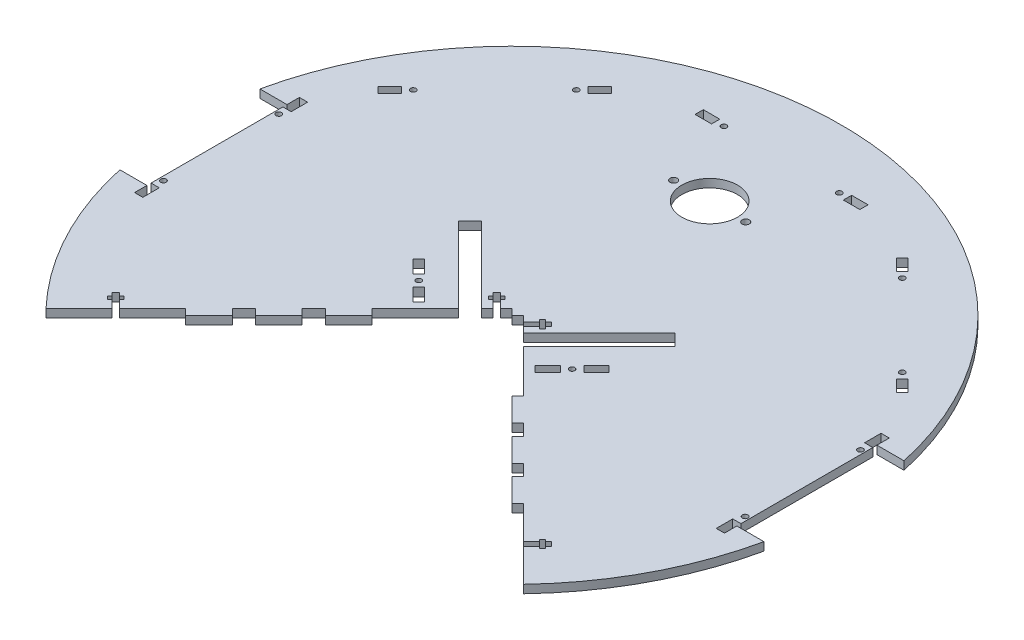
SolidWorks part; units mm, degrees
ref_plane "Front Plane" through (0, 0, 0) normal (0, 0, 1) x (1, 0, 0)
ref_plane "Top Plane" through (0, 0, 0) normal (0, 1, 0) x (1, 0, 0)
ref_plane "Right Plane" through (0, 0, 0) normal (1, 0, 0) x (0, 0, -1)
sketch "Sketch1" plane through (0, 0, 0) normal (0, 1, 0) x (1, 0, 0)
  circle A0 centre (0, 0) radius 254
  dimension "D1" = 508
extrude "Base Plate" add sketch "Sketch1" along normal blind 6.35
sketch "Sketch2" plane through (0, 6.35, 0) normal (0, 1, 0) x (1, 0, 0)
  line L0 (0, 0) -> (-179.6051, -179.6051)
  line L1 (0, -36.2008) -> (0, -54.9716) construction
  line L2 (0, 0) -> (179.6051, -179.6051)
  circle A0 centre (0, 0) radius 254 construction
  arc A1 (-179.6051, -179.6051) -> (179.6051, -179.6051) centre (0, 0) ccw
  dimension "D1" = 254
  dimension "D2" = 45
extrude "V Funnel Cut" cut sketch "Sketch2" against normal through all
sketch "Sketch4" plane through (0, 6.35, 0) normal (0, 1, 0) x (1, 0, 0)
  line L0 (0, 54.2551) -> (0, 121.7464) construction
  line L1 (-251.46, 53.975) -> (-229.87, 53.975)
  line L2 (-254, 51.435) -> (-254, -51.435)
  line L3 (-251.46, -53.975) -> (-229.87, -53.975)
  line L4 (-227.33, 51.435) -> (-227.33, -51.435)
  line L5 (-17.8666, 0) -> (24.1783, 0) construction
  line L6 (-254, -69.5481) -> (-254, -224.3367) construction
  line L8 (-254, 53.975) -> (-227.33, 53.975)
  line L9 (-254, 53.975) -> (-254, -53.975)
  line L10 (-254, -53.975) -> (-227.33, -53.975)
  line L11 (-227.33, 53.975) -> (-227.33, -53.975)
  arc A0 (-251.46, -53.975) -> (-254, -51.435) centre (-251.46, -51.435) cw
  arc A1 (-229.87, -53.975) -> (-227.33, -51.435) centre (-229.87, -51.435) ccw
  arc A2 (-227.33, 51.435) -> (-229.87, 53.975) centre (-229.87, 51.435) ccw
  arc A3 (-251.46, 53.975) -> (-254, 51.435) centre (-251.46, 51.435) ccw
  arc A4 (179.6051, -179.6051) -> (-179.6051, -179.6051) centre (0, 0) ccw construction
  arc M13 (179.6051, -179.6051) -> (-179.6051, -179.6051) centre (0, 0) ccw
  dimension "D5" = 2.54
  dimension "D4" = 2.54
  dimension "D1" = 26.67
  dimension "D3" = 107.95
extrude "Wheel Hole Slot" cut sketch "Sketch4" against normal through all contours A3 L8 L9 | L1 A3 L2 M13 | L4 A2 L1 L3 A1 M13 | A2 L11 L8 | A0 L3 L2 M13 | L10 A0 L9 | A1 L10 L11 region at (-253.4326, 6.35, -53.4076) region at (-252.2473, 6.35, -40.3381) region at (-239.7752, 6.35, 0) region at (-227.8974, 6.35, -53.4076) region at (-252.2473, 6.35, 40.3381) region at (-253.4326, 6.35, 53.4076) region at (-227.8974, 6.35, 53.4076)
mirror "Wheel Slot Mirror" about plane through (0, 0, 0) normal (1, 0, 0) of "Wheel Hole Slot"
sketch "Sketch6" plane through (0, 6.35, 0) normal (0, 1, 0) x (1, 0, 0)
  line L0 (-35.921, -35.921) -> (-20.8354, -51.0067) construction
  line L1 (0, 0) -> (-179.6051, -179.6051) construction
  line L2 (179.6051, -179.6051) -> (0, 0) construction
  line B0 (-61.3685, -5.9835) -> (-71.1005, 3.7485)
  line B1 (-61.3685, -5.9835) -> (-65.8586, -10.4736)
  line B2 (-71.1005, 3.7485) -> (-75.5906, -0.7416)
  line B3 (-65.8586, -10.4736) -> (-75.5906, -0.7416)
  line B4 (-52.3882, -14.9637) -> (-42.6562, -24.6957)
  line B5 (-56.8783, -19.4538) -> (-47.1463, -29.1858)
  line B6 (-42.6562, -24.6957) -> (-47.1463, -29.1858)
  line B7 (-52.3882, -14.9637) -> (-56.8783, -19.4538)
  circle B8 centre (-59.1234, -12.7186) radius 2.0955
  dimension "D1" = 50.8
  dimension "D2" = 12.7
sketch_block_instance "BoltTab-1"
sketch_block "BoltTab" parameters "D1"=4.191, "D2"=6.35, "D3"=6.35
extrude "Arm Post Connector" cut sketch "Sketch6" against normal through all
mirror "Arm Post Connector Mirror" about plane through (0, 0, 0) normal (1, 0, 0) of "Arm Post Connector"
sketch "Sketch8" plane through (0, 0, 0) normal (0, -1, 0) x (1, 0, 0)
  line L0 (-227.33, -63.5) -> (-227.33, -50.8) construction
  line L1 (-227.33, -63.5) -> (-220.98, -63.5) construction
  line L2 (-220.98, -63.5) -> (-220.98, -50.8) construction
  line L3 (-227.33, -50.8) -> (-220.98, -50.8) construction
  line L4 (-227.33, -63.5) -> (-227.33, -50.8)
  line L5 (-227.33, -63.5) -> (-220.98, -63.5)
  line L6 (-220.98, -63.5) -> (-220.98, -50.8)
  line L7 (-227.33, -50.8) -> (-220.98, -50.8)
  line L8 (-227.33, 50.8) -> (-220.98, 50.8) construction
  line L9 (-227.33, 63.5) -> (-227.33, 50.8) construction
  line L10 (-220.98, 63.5) -> (-220.98, 50.8) construction
  line L11 (-227.33, 63.5) -> (-220.98, 63.5) construction
  line L12 (-227.33, 50.8) -> (-220.98, 50.8)
  line L13 (-227.33, 63.5) -> (-227.33, 50.8)
  line L14 (-220.98, 63.5) -> (-220.98, 50.8)
  line L15 (-227.33, 63.5) -> (-220.98, 63.5)
  line L16 (-227.33, -46.5836) -> (-220.98, -46.5836) construction
  line L17 (-227.33, -42.3164) -> (-220.98, -42.3164) construction
  line L18 (-227.33, -46.5836) -> (-220.98, -46.5836) construction
  line L19 (-227.33, -42.3164) -> (-220.98, -42.3164) construction
  line L20 (-224.155, -42.3164) -> (-224.155, -46.5836) construction
  line L21 (-227.33, 42.3164) -> (-220.98, 42.3164) construction
  line L22 (-227.33, 46.5836) -> (-220.98, 46.5836) construction
  line L23 (-227.33, 42.3164) -> (-220.98, 42.3164) construction
  line L24 (-227.33, 46.5836) -> (-220.98, 46.5836) construction
  line L25 (-224.155, 42.3164) -> (-224.155, 46.5836) construction
  circle A0 centre (-224.155, -44.45) radius 2.1336
  circle A1 centre (-224.155, 44.45) radius 2.1336
extrude "Motor Mount Connector" cut sketch "Sketch8" against normal through all
mirror "Motor Mount Connector Mirror" about plane through (0, 0, 0) normal (1, 0, 0) of "Motor Mount Connector"
sketch "Sketch9" plane through (0, 0, 0) normal (0, -1, 0) x (1, 0, 0)
  line L0 (-63.5, -204.6423) -> (-63.5, -210.9923) construction
  line L1 (-63.5, -204.6423) -> (-50.8, -204.6423) construction
  line L2 (-50.8, -204.6423) -> (-50.8, -210.9923) construction
  line L3 (-63.5, -210.9923) -> (-50.8, -210.9923) construction
  line L4 (-63.5, -204.6423) -> (-63.5, -210.9923)
  line L5 (-63.5, -204.6423) -> (-50.8, -204.6423)
  line L6 (-50.8, -204.6423) -> (-50.8, -210.9923)
  line L7 (-63.5, -210.9923) -> (-50.8, -210.9923)
  line L8 (-46.5836, -204.6423) -> (-46.5836, -210.9923) construction
  line L9 (-42.3164, -204.6423) -> (-42.3164, -210.9923) construction
  line L10 (-46.5836, -204.6423) -> (-46.5836, -210.9923) construction
  line L11 (-42.3164, -204.6423) -> (-42.3164, -210.9923) construction
  line L12 (-46.5836, -207.8173) -> (-42.3164, -207.8173) construction
  line L13 (42.3164, -204.6423) -> (42.3164, -210.9923) construction
  line L14 (46.5836, -204.6423) -> (46.5836, -210.9923) construction
  line L15 (42.3164, -204.6423) -> (42.3164, -210.9923) construction
  line L16 (46.5836, -204.6423) -> (46.5836, -210.9923) construction
  line L17 (50.8, -210.9923) -> (63.5, -210.9923)
  line L18 (63.5, -210.9923) -> (63.5, -204.6423)
  line L19 (63.5, -204.6423) -> (50.8, -204.6423)
  line L20 (50.8, -204.6423) -> (50.8, -210.9923)
  line L21 (50.8, -210.9923) -> (63.5, -210.9923)
  line L22 (63.5, -210.9923) -> (63.5, -204.6423)
  line L23 (63.5, -204.6423) -> (50.8, -204.6423)
  line L24 (50.8, -204.6423) -> (50.8, -210.9923)
  line L25 (42.3164, -207.8173) -> (46.5836, -207.8173) construction
  circle A0 centre (-44.45, -207.8173) radius 2.1336
  circle A1 centre (44.45, -207.8173) radius 2.1336
  dimension "D1" = 0
extrude "Back Mount Connector" cut sketch "Sketch9" against normal through all
sketch "Sketch10" plane through (0, 0, 0) normal (0, -1, 0) x (1, 0, 0)
  line L0 (-204.1857, -101.143) -> (-195.2055, -110.1232) construction
  line L1 (-195.2055, -110.1232) -> (-190.7153, -105.6331) construction
  line L2 (-190.7153, -105.6331) -> (-199.6956, -96.6529) construction
  line L3 (-199.6956, -96.6529) -> (-204.1857, -101.143) construction
  line L4 (-123.3634, -181.9653) -> (-114.3832, -190.9455) construction
  line L5 (-114.3832, -190.9455) -> (-109.893, -186.4554) construction
  line L6 (-109.893, -186.4554) -> (-118.8733, -177.4752) construction
  line L7 (-118.8733, -177.4752) -> (-123.3634, -181.9653) construction
  line L8 (-204.1857, -101.143) -> (-195.2055, -110.1232)
  line L9 (-195.2055, -110.1232) -> (-190.7153, -105.6331)
  line L10 (-190.7153, -105.6331) -> (-199.6956, -96.6529)
  line L11 (-199.6956, -96.6529) -> (-204.1857, -101.143)
  line L12 (-123.3634, -181.9653) -> (-114.3832, -190.9455)
  line L13 (-114.3832, -190.9455) -> (-109.893, -186.4554)
  line L14 (-109.893, -186.4554) -> (-118.8733, -177.4752)
  line L15 (-118.8733, -177.4752) -> (-123.3634, -181.9653)
  line L16 (-187.7339, -108.6146) -> (-192.224, -113.1047) construction
  line L17 (-184.7165, -111.6319) -> (-189.2067, -116.122) construction
  line L18 (-124.8721, -171.4763) -> (-129.3622, -175.9665) construction
  line L19 (-121.8547, -174.4937) -> (-126.3449, -178.9838) construction
  line L20 (-187.7339, -108.6146) -> (-192.224, -113.1047) construction
  line L21 (-184.7165, -111.6319) -> (-189.2067, -116.122) construction
  line L22 (-124.8721, -171.4763) -> (-129.3622, -175.9665) construction
  line L23 (-121.8547, -174.4937) -> (-126.3449, -178.9838) construction
  line L25 (-186.9616, -113.877) -> (-189.979, -110.8596) construction
  line L26 (-127.1172, -173.7214) -> (-124.0998, -176.7388) construction
  circle A0 centre (-188.4703, -112.3683) radius 2.1336
  circle A1 centre (-125.6085, -175.2301) radius 2.1336
extrude "Side Ass Connector" cut sketch "Sketch10" against normal through all
mirror "Side Ass Connector Mirror" about plane through (0, 0, 0) normal (1, 0, 0) of "Side Ass Connector"
sketch "Sketch11" plane through (0, 6.35, 0) normal (0, 1, 0) x (1, 0, 0)
  line L0 (0, 61.4305) -> (0, 100.7164) construction
  line L1 (-82.8279, 254) -> (68.7629, 254) construction
  circle A0 centre (0, 152.4) radius 21.463
  circle A2 centre (27.7813, 152.4) radius 2.7781 construction
  circle A3 centre (-27.7813, 152.4) radius 2.7781 construction
  circle A4 centre (27.7813, 152.4) radius 2.7781
  circle A5 centre (-27.7813, 152.4) radius 2.7781
  arc A6 (248.1989, 53.975) -> (-248.1989, 53.975) centre (0, 0) ccw construction
  dimension "D1" = 42.926
  dimension "D2" = 101.6
extrude "Caster Wheel Hole" cut sketch "Sketch11" against normal through all
sketch "Sketch12" plane through (0, 0, 0) normal (0.7071, 0, 0.7071) x (0.7071, 0, -0.7071)
  line L0 (-177.8, 6.35) -> (-177.8, 0) construction
  line L1 (-254, 6.35) -> (-177.8, 6.35)
  line L2 (-254, 6.35) -> (-254, 0)
  line L3 (-254, 0) -> (-177.8, 0)
  line L4 (-177.8, 6.35) -> (-177.8, 0)
  line L5 (0, 0) -> (-254, 0) construction
  line L6 (0, 6.35) -> (-254, 6.35) construction
  line L7 (-152.4, 6.35) -> (-139.7, 6.35)
  line L8 (-152.4, 6.35) -> (-152.4, 0)
  line L9 (-152.4, 0) -> (-139.7, 0)
  line L10 (-139.7, 6.35) -> (-139.7, 0)
  line L11 (-152.4, 0) -> (-152.4, 6.35) construction
  line L12 (-139.7, 6.35) -> (-139.7, 0) construction
  line L13 (-114.3, 0) -> (-114.3, 6.35) construction
  line L14 (-114.3, 6.35) -> (-101.6, 6.35)
  line L15 (-114.3, 6.35) -> (-114.3, 0)
  line L16 (-114.3, 0) -> (-101.6, 0)
  line L17 (-101.6, 6.35) -> (-101.6, 0)
  line L18 (-101.6, 6.35) -> (-101.6, 0) construction
  line L19 (-76.2, 0) -> (-76.2, 6.35) construction
  line L20 (-76.2, 6.35) -> (0, 6.35)
  line L21 (-76.2, 6.35) -> (-76.2, 0)
  line L22 (-76.2, 0) -> (0, 0)
  line L23 (0, 6.35) -> (0, 0)
extrude "V Funnel Tabs" cut sketch "Sketch12" against normal blind 6.35
mirror "V Funnel Tab Mirror" about plane through (0, 0, 0) normal (1, 0, 0) of "V Funnel Tabs"
sketch "Sketch13" plane through (0, 6.35, 0) normal (0, 1, 0) x (1, 0, 0)
  line L0 (-11.6893, -11.6893) -> (-20.6696, -20.6696)
  line L1 (-11.6893, -11.6893) -> (-74.5511, 51.1725)
  line L2 (-20.6696, -20.6696) -> (-83.5314, 42.1922)
  line L3 (-74.5511, 51.1725) -> (-83.5314, 42.1922)
  line L4 (-58.3717, -49.3914) -> (-53.8815, -53.8815) construction
  line L8 (-53.8815, -53.8815) -> (-71.842, -71.842) construction
  line L10 (55.6675, -88.0264) -> (50.4158, -82.7747) construction
  line L11 (-137795.0233, 137762.6644) -> (172087.8094, -172120.1683) construction
  dimension "D1" = 88.9
  dimension "D2" = 12.7
extrude "Peg Clearance" cut sketch "Sketch13" against normal through all
mirror "Peg Clearance Mirror" about plane through (0, 0, 0) normal (1, 0, 0) of "Peg Clearance"
sketch "Sketch14" plane through (0, 6.35, 0) normal (0, 1, 0) x (1, 0, 0)
  line L0 (-30.6253, 18.936) -> (5.9619, -17.6512) construction
  line L1 (-16.1795, -7.1992) -> (-4.4901, 4.4901) construction
  line L3 (0, 0) -> (-4.4901, 4.4901) construction
  line L4 (-16.1795, -7.1992) -> (-74.5511, 51.1725) construction
  line B0 (-11.8435, -2.8632) -> (-8.8261, 0.1541)
  line B1 (-17.2675, 8.5956) -> (-15.6331, 10.23)
  line B2 (-15.6331, 10.23) -> (-13.3881, 7.9849)
  line B3 (-13.3881, 7.9849) -> (-15.0225, 6.3505)
  line B4 (-15.0225, 6.3505) -> (-8.8261, 0.1541)
  line B5 (-17.2675, 8.5956) -> (-19.6024, 10.9305)
  line B6 (-19.6024, 10.9305) -> (-22.6198, 7.9131)
  line B7 (-20.2849, 5.5782) -> (-22.6198, 7.9131)
  line B8 (-18.0398, 3.3332) -> (-11.8435, -2.8632)
  line B9 (-19.6743, 1.6988) -> (-18.0398, 3.3332)
  line B10 (-21.9193, 3.9438) -> (-19.6743, 1.6988)
  line B11 (-20.2849, 5.5782) -> (-21.9193, 3.9438)
sketch_block_instance "TSlot-1"
sketch_block "TSlot" parameters "D1"=3.302, "D2"=3.175
extrude "V Funnel T Slot 1" cut sketch "Sketch14" against normal through all
sketch "Sketch15" plane through (0, 6.35, 0) normal (0, 1, 0) x (1, 0, 0)
  line L0 (-123.3007, -182.028) -> (-191.14, -114.1887) construction
  line L1 (-130.2137, -121.2335) -> (-125.7236, -125.7236) construction
  line L2 (-179.6051, -179.6051) -> (-184.0953, -175.115) construction
  line L3 (-184.0953, -175.115) -> (-176.6237, -167.6434) construction
  line B0 (-158.6632, -149.6829) -> (-155.6458, -146.6655)
  line B1 (-164.0872, -138.2241) -> (-162.4528, -136.5897)
  line B2 (-162.4528, -136.5897) -> (-160.2078, -138.8348)
  line B3 (-160.2078, -138.8348) -> (-161.8422, -140.4692)
  line B4 (-161.8422, -140.4692) -> (-155.6458, -146.6655)
  line B5 (-164.0872, -138.2241) -> (-166.4221, -135.8892)
  line B6 (-166.4221, -135.8892) -> (-169.4395, -138.9066)
  line B7 (-167.1046, -141.2415) -> (-169.4395, -138.9066)
  line B8 (-164.8595, -143.4865) -> (-158.6632, -149.6829)
  line B9 (-166.4939, -145.1209) -> (-164.8595, -143.4865)
  line B10 (-168.739, -142.8759) -> (-166.4939, -145.1209)
  line B11 (-167.1046, -141.2415) -> (-168.739, -142.8759)
sketch_block_instance "TSlot-3"
extrude "V Funnel T Slot 2" cut sketch "Sketch15" against normal through all
mirror "Mirror1" about plane through (0, 0, 0) normal (1, 0, 0) of "V Funnel T Slot 2", "V Funnel T Slot 1"
